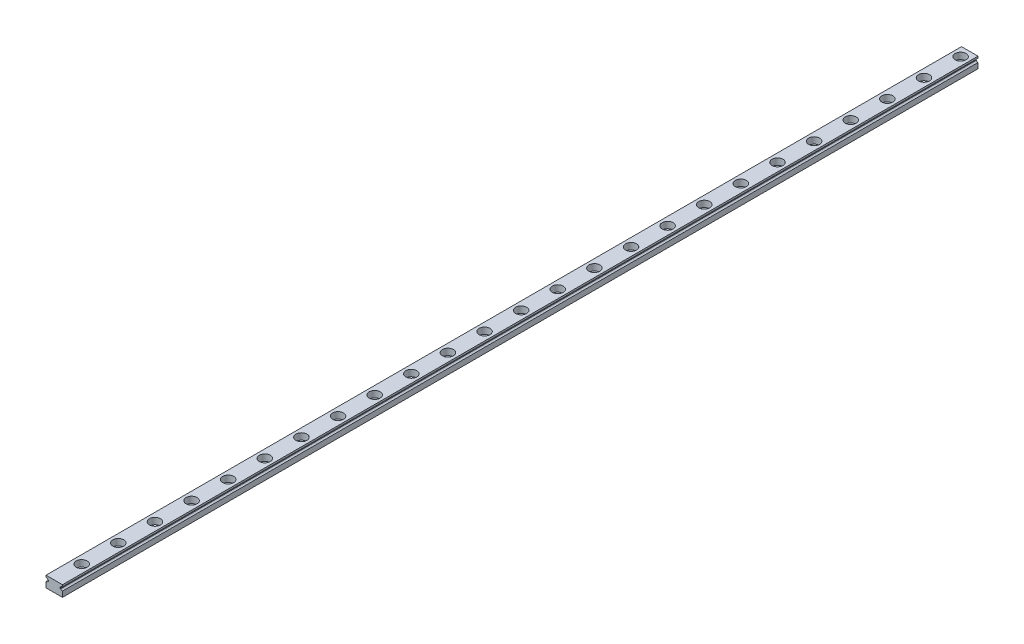
SolidWorks part; units mm, degrees
ref_plane "Front Plane" through (0, 0, 0) normal (0, 0, 1) x (1, 0, 0)
ref_plane "Top Plane" through (0, 0, 0) normal (0, 1, 0) x (1, 0, 0)
ref_plane "Right Plane" through (0, 0, 0) normal (1, 0, 0) x (0, 0, -1)
sketch "Sketch1" plane through (0, 0, 0) normal (0, 0, 1) x (1, 0, 0)
  line L0 (0, 0) -> (0, 5.7299) construction
  line L1 (-4.5, -3) -> (4.5, -3)
  line L2 (-4.5, -3) -> (-4.5, 0)
  line L3 (-4.5, 3) -> (4.5, 3)
  line L4 (4.5, -3) -> (4.5, 0)
  line L5 (-4.5, -3) -> (4.5, 3) construction
  line L6 (-4.5, 3) -> (4.5, -3) construction
  line L7 (-4.5, 2) -> (-4.5, 3)
  line L8 (-3.564, 0.648) -> (-3.2351, 0.648)
  line L9 (3.564, 0.648) -> (3.2351, 0.648)
  line L10 (-3.564, 1.352) -> (-3.2351, 1.352)
  line L11 (-3.2351, 0.648) -> (-3.2351, 1.352)
  line L12 (3.2351, 0.648) -> (3.2351, 1.352)
  line L13 (3.564, 1.352) -> (3.2351, 1.352)
  line L14 (4.5, 2) -> (4.5, 3)
  arc A0 (-3.564, 1.352) -> (-4.5, 2) centre (-4.5, 1) ccw
  arc A1 (-4.5, 0) -> (-3.564, 0.648) centre (-4.5, 1) ccw
  arc A2 (4.5, 0) -> (3.564, 0.648) centre (4.5, 1) cw
  arc A3 (3.564, 1.352) -> (4.5, 2) centre (4.5, 1) cw
  point P0 (0, 0)
  dimension "D3" = 1
  dimension "D1" = 9
  dimension "D2" = 6
  dimension "D4" = 2
extrude "Extrude1" add sketch "Sketch1" along normal blind 500
sketch "Sketch2" plane through (0, 3, 0) normal (0, 1, 0) x (1, 0, 0)
  line L0 (4.5, 0) -> (-4.5, 0) construction
  circle A0 centre (0, -5) radius 1.75
  circle A1 centre (0, -5) radius 3
  dimension "D1" = 3.5
  dimension "D2" = 6
  dimension "D3" = 5
extrude "Extrude2" cut sketch "Sketch2" against normal blind 3.5 contours A1
extrude "Extrude3" cut sketch "Sketch" against normal through all contours A0
sketch "Sketch" plane through (0, 3, 0) normal (0, 1, 0) x (1, 0, 0) same geometry as "Sketch2"
pattern_linear "LPattern1" count 30 spacing 20 along (0, 0, 1) of "Extrude2", "Extrude3"
